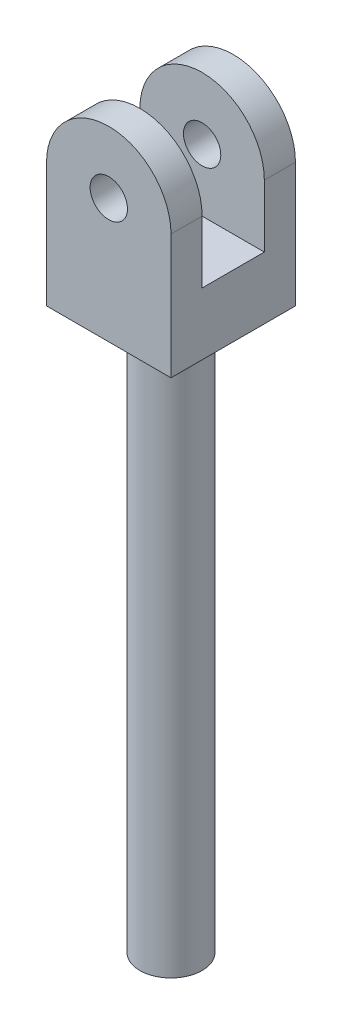
SolidWorks part; units mm, degrees
ref_plane "Alzado" through (0, 0, 0) normal (0, 0, 1) x (1, 0, 0)
ref_plane "Planta" through (0, 0, 0) normal (0, 1, 0) x (1, 0, 0)
ref_plane "Vista lateral" through (0, 0, 0) normal (1, 0, 0) x (0, 0, -1)
sketch "Croquis1" plane through (0, 0, 0) normal (0, 0, 1) x (1, 0, 0)
  line L0 (-5, 0) -> (-5, -10)
  line L1 (-5, -10) -> (5, -10)
  line L2 (5, -10) -> (5, 0)
  line L3 (0, 5) -> (-12.3649, 5) construction
  circle A0 centre (0, 0) radius 1.5
  arc A1 (5, 0) -> (-5, 0) centre (0, 0) ccw
  dimension "D1" = 3
  dimension "D2" = 10
  dimension "D3" = 15
extrude "Saliente-Extruir1" add sketch "Croquis1" along normal blind 10
sketch "Croquis2" plane through (0, -10, 0) normal (0, -1, 0) x (1, 0, 0)
  line L0 (-5, 5) -> (5, 5) construction
  line L1 (-5, 10) -> (-5, 0) construction
  line L2 (5, 10) -> (5, 0) construction
  circle A0 centre (0, 5) radius 2.5
  dimension "D1" = 5
extrude "Saliente-Extruir2" add sketch "Croquis2" along normal blind 45
ref_plane "Plano1" through (0, 0, 5) normal (0, 0, 1) x (1, 0, 0)
ref_axis "Eje1" through (0, 7, 5) along (0, -1, 0)
sketch "Croquis3" plane through (-5, 0, 0) normal (-1, 0, 0) x (0, 0, 1)
  line L0 (10, 5) -> (0, 5) construction
  line L1 (2.5, 5) -> (7.5, 5)
  line L2 (2.5, 5) -> (2.5, -5)
  line L3 (2.5, -5) -> (7.5, -5)
  line L4 (7.5, 5) -> (7.5, -5)
  line L6 (0, 0) -> (0, -10) construction
  point P6 (0, -5)
  dimension "D1" = 5
  dimension "D2" = 2.5
  dimension "D3" = 10
extrude "Cortar-Extruir1" cut sketch "Croquis3" against normal blind 40
ref_plane "Plano2" through (0, 0, 5) normal (0, 0, 1) x (1, 0, 0)
ref_axis "Eje2" through (0, 8, 5) along (0, -1, 0)
ref_plane "Plano3" through (2.462, 0, 2.9341) normal (-0.6428, 0, -0.766) x (-0.766, 0, 0.6428)
